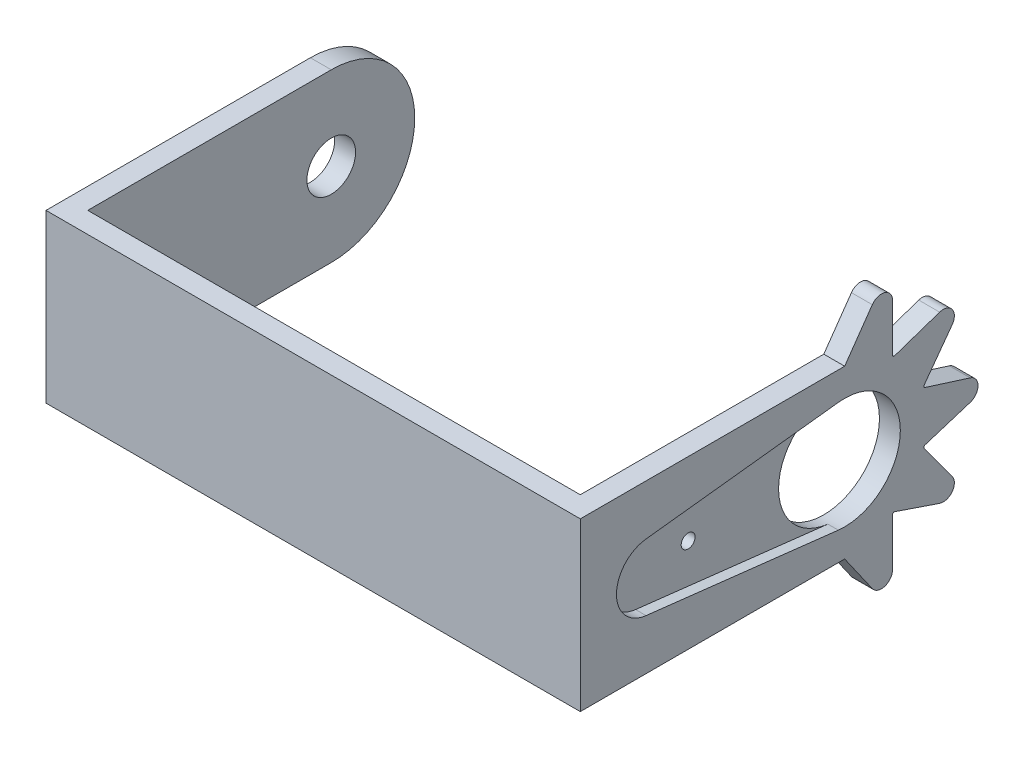
SolidWorks part; units mm, degrees
material "ABS"
ref_plane "前视基准面" through (0, 0, 0) normal (0, 0, 1) x (1, 0, 0)
ref_plane "上视基准面" through (0, 0, 0) normal (0, 1, 0) x (1, 0, 0)
ref_plane "右视基准面" through (0, 0, 0) normal (1, 0, 0) x (0, 0, -1)
sketch "草图2" plane through (0, 0, 0) normal (0, 1, 0) x (1, 0, 0)
  line L0 (0, 0) -> (38.4, 0)
  line L1 (38.4, 0) -> (38.4, 25)
  line L2 (38.4, 25) -> (36.9, 25)
  line L3 (36.9, 25) -> (36.9, 1.5)
  line L4 (36.9, 1.5) -> (1.5, 1.5)
  line L5 (1.5, 1.5) -> (1.5, 25)
  line L6 (1.5, 25) -> (0, 25)
  line L7 (0, 25) -> (0, 0)
  dimension "D1" = 1.5
  dimension "D2" = 25
  dimension "D3" = 1.5
  dimension "D4" = 38.4
extrude "凸台-拉伸2" add sketch "草图2" along normal blind 12
fillet "圆角1" radius 6 4 edges at (0.75, 0, -25) (0.75, 12, -25) (37.65, 0, -25) (37.65, 12, -25)
sketch "草图3" plane through (38.4, 0, 0) normal (1, 0, 0) x (0, 0, -1)
  line L0 (18.5429, 9.9738) -> (4.7257, 8.3843)
  line L1 (4.7257, 3.6157) -> (18.5429, 2.0262)
  arc A0 (18.5429, 9.9738) -> (18.5429, 2.0262) centre (19, 6) cw
  arc A1 (4.7257, 8.3843) -> (4.7257, 3.6157) centre (5, 6) ccw
  dimension "D1" = 4
  dimension "D2" = 2.4
  dimension "D3" = 14
extrude "切除-拉伸1" cut sketch "草图3" against normal blind 0.75
sketch "草图4" plane through (37.65, 0, 0) normal (1, 0, 0) x (0, 0, -1)
  circle A0 centre (19, 6) radius 4
  dimension "D1" = 8
extrude "切除-拉伸2" cut sketch "草图4" against normal up to next
sketch "草图5" plane through (0, 0, 0) normal (-1, 0, 0) x (0, 0, 1)
  circle A0 centre (-19, 6) radius 1.75
  dimension "D1" = 3.5
extrude "切除-拉伸3" cut sketch "草图5" against normal up to next
sketch "草图6" plane through (37.65, 0, 0) normal (1, 0, 0) x (0, 0, -1)
  circle A0 centre (8.5, 6) radius 0.5
  arc A2 (18.5429, 9.9738) -> (18.5429, 2.0262) centre (19, 6) ccw construction
  circle A3 centre (19, 6) radius 1.75 construction
  point P9 (15, 6)
  dimension "D1" = 1
  dimension "D2" = 10.5
extrude "切除-拉伸4" cut sketch "草图6" against normal up to next
sketch "草图7" plane through (38.4, 0, 0) normal (1, 0, 0) x (0, 0, -1)
  line L0 (19, 12) -> (20.9861, 14.8365)
  line L1 (22.4415, 14.3776) -> (22.4415, 10.9149)
  line L2 (26.7291, 10.7211) -> (24.6816, 7.9286)
  line L3 (22.5479, 10.8387) -> (25.8268, 11.9517)
  line L4 (28.0248, 5.237) -> (24.7223, 4.1958)
  line L5 (24.7223, 7.8042) -> (28.0248, 6.763)
  line L6 (25.8268, 0.0483) -> (22.5479, 1.1613)
  line L7 (24.6816, 4.0714) -> (26.7291, 1.2789)
  line L8 (20.9861, -2.8365) -> (19, 0)
  line L9 (22.4415, 1.0851) -> (22.4415, -2.3776)
  arc A0 (25, 6) -> (19, 12) centre (19, 6) ccw construction
  arc A1 (19, 12) -> (22.4415, 10.9149) centre (19, 6) cw
  arc A2 (22.4415, 14.3776) -> (20.9861, 14.8365) centre (21.6415, 14.3776) ccw
  arc A3 (22.5479, 10.8387) -> (24.6816, 7.9286) centre (19, 6) cw
  arc A4 (26.7291, 10.7211) -> (25.8268, 11.9517) centre (26.084, 11.1942) ccw
  arc A5 (24.7223, 7.8042) -> (24.7223, 4.1958) centre (19, 6) cw
  arc A6 (28.0248, 5.237) -> (28.0248, 6.763) centre (27.7842, 6) ccw
  arc A7 (24.6816, 4.0714) -> (22.5479, 1.1613) centre (19, 6) cw
  arc A8 (25.8268, 0.0483) -> (26.7291, 1.2789) centre (26.084, 0.8058) ccw
  arc A9 (22.4415, 1.0851) -> (19, 0) centre (19, 6) cw
  arc A10 (20.9861, -2.8365) -> (22.4415, -2.3776) centre (21.6415, -2.3776) ccw
  point P10 (22.4415, 16.9149)
  point P34 (19, 6)
  dimension "D3" = 0.8
  dimension "D1" = 6
  dimension "D2" = 35
  dimension "D4" = 5
extrude "凸台-拉伸4" add sketch "草图7" against normal up to surface (1.5 mm away) up to face at (36.9, 6, -9)
